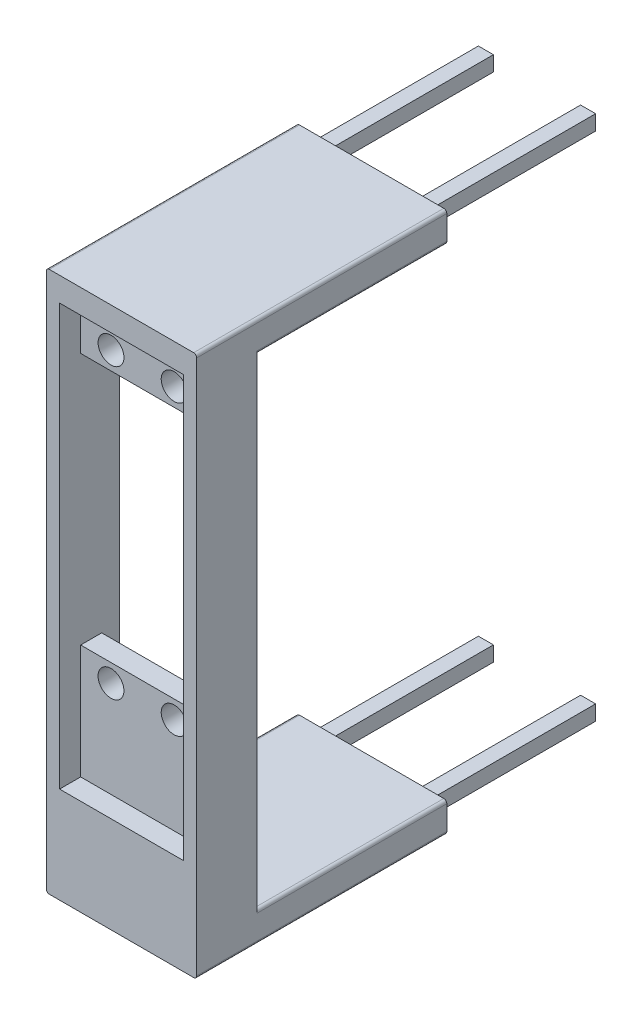
SolidWorks part; units mm, degrees
ref_plane "Front Plane" through (0, 0, 0) normal (0, 0, 1) x (1, 0, 0)
ref_plane "Top Plane" through (0, 0, 0) normal (0, 1, 0) x (1, 0, 0)
ref_plane "Right Plane" through (0, 0, 0) normal (1, 0, 0) x (0, 0, -1)
sketch "Sketch2" plane through (0, 0, -60.1331) normal (0, 0, 1) x (1, 0, 0)
  line L0 (165.5709, -7.7744) -> (110.5709, -7.7744) construction
  line L5 (113.0709, -2.7744) -> (138.0709, -2.7744)
  line L6 (113.0709, -2.7744) -> (113.0709, -7.7744)
  line L7 (113.0709, -7.7744) -> (138.0709, -7.7744)
  line L8 (138.0709, -2.7744) -> (138.0709, -7.7744)
  line L9 (110.5709, -2.7744) -> (160.5709, -2.7744) construction
  line L10 (165.5709, 82.2256) -> (110.5709, 82.2256) construction
  line L11 (113.0709, 82.2256) -> (138.0709, 82.2256)
  line L12 (113.0709, 82.2256) -> (113.0709, 77.2256)
  line L13 (113.0709, 77.2256) -> (138.0709, 77.2256)
  line L14 (138.0709, 82.2256) -> (138.0709, 77.2256)
  line L17 (115.5709, -5.2744) -> (113.0709, -5.2744)
  line L18 (115.5709, -3.7744) -> (115.5709, -6.7744) construction
  line L19 (135.5709, -5.2744) -> (138.0709, -5.2744)
  line L20 (160.5709, 77.2256) -> (110.5709, 77.2256) construction
  line L21 (135.5709, -3.7744) -> (135.5709, -6.7744) construction
  line M13 (165.5709, 82.2256) -> (110.5709, 82.2256)
  line M15 (110.5709, 77.2256) -> (160.5709, 77.2256)
  line M19 (160.5709, -2.7744) -> (110.5709, -2.7744)
  line M21 (110.5709, -7.7744) -> (165.5709, -7.7744)
  line M23 (115.5709, -3.7744) -> (118.5709, -3.7744)
  line M24 (118.5709, -3.7744) -> (118.5709, -6.7744)
  line M25 (118.5709, -6.7744) -> (115.5709, -6.7744)
  line M26 (115.5709, -6.7744) -> (115.5709, -3.7744)
  line M27 (132.5709, 81.2256) -> (135.5709, 81.2256)
  line M28 (135.5709, 81.2256) -> (135.5709, 78.2256)
  line M29 (135.5709, 78.2256) -> (132.5709, 78.2256)
  line M30 (132.5709, 78.2256) -> (132.5709, 81.2256)
  line M31 (115.5709, 81.2256) -> (118.5709, 81.2256)
  line M32 (118.5709, 81.2256) -> (118.5709, 78.2256)
  line M33 (118.5709, 78.2256) -> (115.5709, 78.2256)
  line M34 (115.5709, 78.2256) -> (115.5709, 81.2256)
  line M35 (132.5709, -3.7744) -> (135.5709, -3.7744)
  line M36 (135.5709, -3.7744) -> (135.5709, -6.7744)
  line M37 (135.5709, -6.7744) -> (132.5709, -6.7744)
  line M38 (132.5709, -6.7744) -> (132.5709, -3.7744)
  dimension "D1" = 25
extrude "Boss-Extrude1" add sketch "Sketch2" along normal up to surface (31.5956 mm away) contours L8 L6 M38 M35 M36 M19 M26 M23 M24 M25 M21 M37 | L14 L12 M13 M15 M34 M31 M32 M33 M30 M27 M28 M29 region at (125.5709, -5.2744, -60.1331) region at (125.5709, 79.7256, -60.1331)
sketch "Sketch3" plane through (0, 0, -60.1331) normal (0, 0, 1) x (1, 0, 0)
  line L0 (165.5709, -7.7744) -> (110.5709, -7.7744) construction
  line L1 (113.0709, 82.2256) -> (138.0709, 82.2256)
  line L2 (113.0709, 82.2256) -> (113.0709, -7.7744)
  line L3 (113.0709, -7.7744) -> (138.0709, -7.7744)
  line L4 (138.0709, 82.2256) -> (138.0709, -7.7744)
sketch "Sketch4" plane through (0, 0, -28.5375) normal (0, 0, 1) x (1, 0, 0)
  line L1 (113.0709, 82.2256) -> (138.0709, 82.2256)
  line L2 (113.0709, 82.2256) -> (113.0709, -7.7744)
  line L3 (113.0709, -7.7744) -> (138.0709, -7.7744)
  line L4 (138.0709, 82.2256) -> (138.0709, -7.7744)
extrude "Boss-Extrude3" add sketch "Sketch4" along normal blind 10
sketch "Sketch6" plane through (0, 0, -18.5375) normal (0, 0, 1) x (1, 0, 0)
  circle A2 centre (120.3209, 72.2256) radius 2.15
  circle A3 centre (130.8209, 72.2256) radius 2.15
  circle A4 centre (130.8209, 24.2256) radius 2.15
  circle A5 centre (120.3209, 24.2256) radius 2.15
  circle A6 centre (130.8209, 72.2256) radius 2.15
  dimension "D1" = 4.3
extrude "Cut-Extrude2" cut sketch "Sketch6" against normal blind 10 contours A4 | A5 | A6 | A2 region at (120.3209, 72.2256, -18.5375) region at (130.8209, 72.2256, -18.5375) region at (130.8209, 24.2256, -18.5375) region at (120.3209, 24.2256, -18.5375)
sketch "Sketch7" plane through (0, 0, -18.5375) normal (0, 0, 1) x (1, 0, 0)
  line L5 (120.3209, 24.2256) -> (120.3209, 27.2256) construction
  line L6 (135.8709, 69.2256) -> (135.8709, 27.2256)
  line L7 (115.2709, 69.2256) -> (135.8709, 69.2256)
  line L9 (115.2709, 27.2256) -> (135.8709, 27.2256)
  line L11 (115.2709, 69.2256) -> (115.2709, 27.2256)
  line L12 (138.0709, -2.7744) -> (138.0709, 77.2256) construction
  line L13 (120.3209, 72.2256) -> (120.3209, 69.2256) construction
  dimension "D1" = 20.6
  dimension "D2" = 42
  dimension "D3" = 2.2
extrude "Cut-Extrude3" cut sketch "Sketch7" against normal blind 10
sketch "Sketch8" plane through (0, 0, -60.1331) normal (0, 0, -1) x (-1, 0, 0)
  line L0 (-135.5709, -3.7744) -> (-135.5709, -6.7744) construction
  line L1 (-135.5709, 81.2256) -> (-132.5709, 81.2256)
  line L2 (-135.5709, 81.2256) -> (-135.5709, 78.2256)
  line L3 (-135.5709, 78.2256) -> (-132.5709, 78.2256)
  line L4 (-132.5709, 81.2256) -> (-132.5709, 78.2256)
  line L5 (-118.5709, 81.2256) -> (-115.5709, 81.2256)
  line L6 (-118.5709, 81.2256) -> (-118.5709, 78.2256)
  line L7 (-118.5709, 78.2256) -> (-115.5709, 78.2256)
  line L8 (-115.5709, 81.2256) -> (-115.5709, 78.2256)
  line L9 (-135.5709, -3.7744) -> (-132.5709, -3.7744)
  line L10 (-135.5709, -3.7744) -> (-135.5709, -6.7744)
  line L11 (-135.5709, -6.7744) -> (-132.5709, -6.7744)
  line L12 (-132.5709, -3.7744) -> (-132.5709, -6.7744)
  line L13 (-135.3209, 80.9756) -> (-132.8209, 78.4756)
  line L14 (-115.5709, -6.7744) -> (-118.5709, -6.7744)
  line L15 (-115.5709, -6.7744) -> (-115.5709, -3.7744)
  line L16 (-115.5709, -3.7744) -> (-118.5709, -3.7744)
  line L17 (-118.5709, -6.7744) -> (-118.5709, -3.7744)
  line L18 (-135.3209, 80.9756) -> (-132.8209, 80.9756)
  line L19 (-135.3209, 80.9756) -> (-135.3209, 78.4756)
  line L20 (-135.3209, 78.4756) -> (-132.8209, 78.4756)
  line L21 (-132.8209, 80.9756) -> (-132.8209, 78.4756)
  line L22 (-135.5709, 81.2256) -> (-132.5709, 78.2256)
  line L23 (-118.5709, 81.2256) -> (-115.5709, 78.2256) construction
  line L24 (-118.3209, 80.9756) -> (-115.8209, 80.9756)
  line L25 (-118.3209, 80.9756) -> (-118.3209, 78.4756)
  line L26 (-118.3209, 78.4756) -> (-115.8209, 78.4756)
  line L27 (-115.8209, 80.9756) -> (-115.8209, 78.4756)
  line L28 (-118.3209, 78.4756) -> (-115.8209, 80.9756)
  line L29 (-135.5709, -3.7744) -> (-132.5709, -6.7744) construction
  line L30 (-135.3209, -4.0244) -> (-132.8209, -4.0244)
  line L31 (-135.3209, -4.0244) -> (-135.3209, -6.5244)
  line L32 (-135.3209, -6.5244) -> (-132.8209, -6.5244)
  line L33 (-132.8209, -4.0244) -> (-132.8209, -6.5244)
  line L34 (-135.3209, -4.0244) -> (-132.8209, -6.5244) construction
  line L35 (-118.3209, -4.0244) -> (-115.8209, -6.5244) construction
  line L36 (-118.3209, -4.0244) -> (-115.8209, -4.0244)
  line L37 (-118.3209, -4.0244) -> (-118.3209, -6.5244)
  line L38 (-118.3209, -6.5244) -> (-115.8209, -6.5244)
  line L39 (-115.8209, -4.0244) -> (-115.8209, -6.5244)
  line L40 (-118.5709, -3.7744) -> (-115.5709, -6.7744) construction
  point P29 (-134.0709, 79.7256)
  point P30 (-134.0709, 79.7256)
  point P35 (-117.0709, 79.7256)
  point P36 (-117.0709, 79.7256)
  point P41 (-134.0709, -5.2744)
  point P42 (-134.0709, -5.2744)
  point P47 (-117.0709, -5.2744)
  point P48 (-117.0709, -5.2744)
  dimension "D1" = 2.5
  dimension "D2" = 2.5
  dimension "D3" = 2.5
  dimension "D4" = 2.5
sketch "Sketch9" plane through (138.0709, 0, 0) normal (1, 0, 0) x (0, 0, -1)
  line L0 (18.5375, 82.2256) -> (60.1331, 82.2256) construction
  line L1 (60.1331, -7.7744) -> (58.1331, -7.7744)
  line L2 (60.1331, -7.7744) -> (60.1331, 82.2256)
  line L3 (60.1331, 82.2256) -> (58.1331, 82.2256)
  line L4 (58.1331, -7.7744) -> (58.1331, 82.2256)
  dimension "D1" = 2
extrude "Cut-Extrude4" cut sketch "Sketch9" against normal through all
sketch "Sketch10" plane through (138.0709, 0, 0) normal (1, 0, 0) x (0, 0, -1)
  line L1 (58.1331, 82.2256) -> (60.1331, 82.2256)
  line L2 (58.1331, 82.2256) -> (58.1331, -7.7744)
  line L3 (58.1331, -7.7744) -> (60.1331, -7.7744)
  line L4 (60.1331, 82.2256) -> (60.1331, -7.7744)
  dimension "D1" = 2
extrude "Boss-Extrude4" add sketch "Sketch10" against normal up to surface (25 mm away) up to face at (113.0709, 37.2256, -40.8353)
extrude "Boss-Extrude5" add sketch "Sketch8" along normal blind 27.5 contours L19 L20 L13 | L21 L18 L13 | L25 L28 L24 | L28 L26 L27 | L39 L36 L37 L38 | L33 L30 L31 L32 region at (133.6542, 80.1423, -60.1331) region at (134.4876, 79.309, -60.1331) region at (117.4876, 80.1423, -60.1331) region at (116.6542, 79.309, -60.1331) region at (134.0709, -5.2744, -60.1331) region at (117.0709, -5.2744, -60.1331)
sketch "Sketch11" plane through (138.0709, 0, 0) normal (1, 0, 0) x (0, 0, -1)
  line L1 (58.1331, 77.2256) -> (61.1331, 77.2256)
  line L2 (58.1331, 77.2256) -> (58.1331, -2.7744)
  line L3 (58.1331, -2.7744) -> (61.1331, -2.7744)
  line L4 (61.1331, 77.2256) -> (61.1331, -2.7744)
  dimension "D1" = 3
extrude "Cut-Extrude5" cut sketch "Sketch11" against normal through all
sketch "Sketch13" plane through (0, 0, -28.5375) normal (0, 0, -1) x (-1, 0, 0)
  line L1 (-135.8709, 75.4756) -> (-115.2709, 75.4756)
  line L2 (-135.8709, 75.4756) -> (-135.8709, 18.4756)
  line L3 (-135.8709, 18.4756) -> (-115.2709, 18.4756)
  line L4 (-115.2709, 75.4756) -> (-115.2709, 18.4756)
  line L8 (-135.8709, 69.2256) -> (-115.2709, 69.2256) construction
  line L9 (-115.2709, 27.2256) -> (-135.8709, 27.2256) construction
  line L10 (-135.8709, 27.2256) -> (-135.8709, 69.2256) construction
  dimension "D1" = 6.25
  dimension "D2" = 8.75
  dimension "D3" = 20.6
extrude "Cut-Extrude6" cut sketch "Sketch13" against normal blind 3
fillet "Fillet1" radius 0.5 8 edges at (138.0709, 82.2256, -39.3353) (138.0709, -7.7744, -39.3353) (113.0709, -7.7744, -39.3353) (113.0709, 82.2256, -39.3353) (113.0709, 77.2256, -44.3353) (113.0709, -2.7744, -44.3353) (138.0709, 77.2256, -44.3353) (138.0709, -2.7744, -44.3353)
sketch "Sketch14" plane through (0, 0, -18.5375) normal (0, 0, 1) x (1, 0, 0)
  line L0 (137.5709, 82.2256) -> (113.5709, 82.2256) construction
  line L1 (115.2709, 78.2256) -> (135.8709, 78.2256)
  line L2 (115.2709, 78.2256) -> (115.2709, 8.2256)
  line L3 (115.2709, 8.2256) -> (135.8709, 8.2256)
  line L4 (135.8709, 78.2256) -> (135.8709, 8.2256)
  line L5 (113.0709, 81.7256) -> (113.0709, -7.2744) construction
  dimension "D1" = 70
  dimension "D2" = 20.6
  dimension "D3" = 4
  dimension "D4" = 2.2
extrude "Cut-Extrude7" cut sketch "Sketch14" against normal blind 3.5
